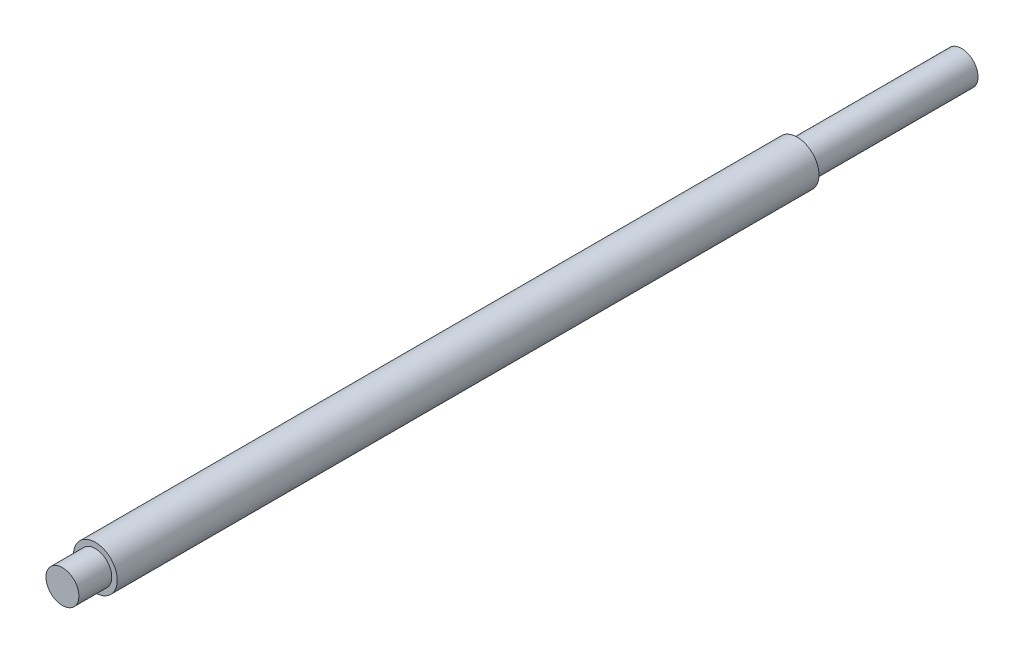
SolidWorks part; units mm, degrees
material "AISI 304"
ref_plane "Front Plane" through (0, 0, 0) normal (0, 0, 1) x (1, 0, 0)
ref_plane "Top Plane" through (0, 0, 0) normal (0, 1, 0) x (1, 0, 0)
ref_plane "Right Plane" through (0, 0, 0) normal (1, 0, 0) x (0, 0, -1)
sketch "Sketch1" plane through (0, 0, 0) normal (0, 0, 1) x (1, 0, 0)
  circle A0 centre (0, 0) radius 6.35
  dimension "D1" = 12.7
extrude "Boss-Extrude1" add sketch "Sketch1" along normal blind 260.35 contours A0
sketch "Sketch2" plane through (0, 0, 0) normal (0, 0, -1) x (-1, 0, 0)
  circle A0 centre (0, 0) radius 6.35
  circle A1 centre (0, 0) radius 4.7625
  circle A2 centre (0, 0) radius 6.35 construction
  dimension "D1" = 9.525
extrude "long-trim" cut sketch "Sketch2" against normal blind 47.625
sketch "Sketch3" plane through (0, 0, 260.35) normal (0, 0, 1) x (1, 0, 0)
  circle A0 centre (0, 0) radius 6.35
  circle A1 centre (0, 0) radius 4.7625
  circle A2 centre (0, 0) radius 6.35 construction
  dimension "D1" = 9.525
extrude "Cut-Extrude2" cut sketch "Sketch3" against normal blind 9.525
sketch "Sketch4" plane through (0, 0, 47.625) normal (0, 0, -1) x (-1, 0, 0)
  circle A0 centre (0, 0) radius 5.08
curve "Helix/Spiral1" pitch 2.54 height 203.2 turns 80
sketch "Sketch5" plane through (0, 0, 0) normal (0, 1, 0) x (1, 0, 0)
  line L0 (6.35, -47.625) -> (5.08, -47.9534)
  line L1 (5.08, -47.9534) -> (5.08, -49.2234)
  line L2 (5.08, -49.2234) -> (6.35, -49.5519)
  line L3 (6.35, -49.5519) -> (6.35, -47.625)
  dimension "D1" = 29
  dimension "D2" = 1.27
  dimension "D3" = 1.27
sweep "Cut-Sweep1" [suppressed] cut profiles "Sketch5" path "Helix/Spiral1"
equation "\"dovetail-angle\"= 55"
equation "\"dovetail-stock-width\"= 5"
equation "\"dovetail-stock-height\"= 1.25"
equation "\"dovetail-depth\"= 0.5 * \"dovetail-stock-height\""
equation "\"dovetail-throat-width\"= \"dovetail-stock-width\" - (2 * \"dovetail-depth\")"
equation "\"delta-x\"= 6"
equation "\"delta-y\"= 3"
equation "\"delta-z\"= 2.5"
equation "\"gib-thickness\"= 0.25"
equation "\"x-slide-length\"= \"dovetail-stock-width\" + \"delta-x\""
equation "\"y-slide-length\"= \"dovetail-stock-width\" + \"delta-y\""
equation "\"dog-point-diam\"= .149"
equation "\"dog-point-length\"= .067"
equation "\"dovetail-double-height\"= 2 * \"dovetail-depth\" + 0.5"
equation "\"acme-major-diam\"= .5"
equation "\"acme-pitch-diam\"= 0.45"
equation "\"D1@Sketch1\"=\"acme-major-diam\""
equation "\"acme-minor-diam\"= 0.4"
equation "\"D1@Boss-Extrude1\"=\"y-screw-length\""
equation "\"acme-nut-od\"= 1.47"
equation "\"acme-nut-length\"= 1"
equation "\"acme-nut-trim-height\"= .75"
equation "\"screw-bearing-od\"= 0.5"
equation "\"screw-bearing-length\"= .375"
equation "\"screw-bearing-id\"= .375"
equation "\"end-plate-thickness\"= \"screw-bearing-length\""
equation "\"D1@Sketch2\"=\"screw-bearing-id\""
equation "\"screw-add-length\"= 2 * \"end-plate-thickness\" + 1 + 0.5"
equation "\"x-screw-length\"= \"x-slide-length\" + \"screw-add-length\""
equation "\"y-screw-length\"= \"y-slide-length\" + \"screw-add-length\""
equation "\"D1@long-trim\"=\"screw-add-length\"-\"end-plate-thickness\""
equation "\"D1@Sketch3\"=\"screw-bearing-id\""
equation "\"D1@Cut-Extrude2\"=\"end-plate-thickness\""
equation "\"acme-nut-mount-hole-space-horz\"= 0.95"
equation "\"acme-nut-mount-hole-space-vert\"= 0.5 * \"acme-nut-length\""
